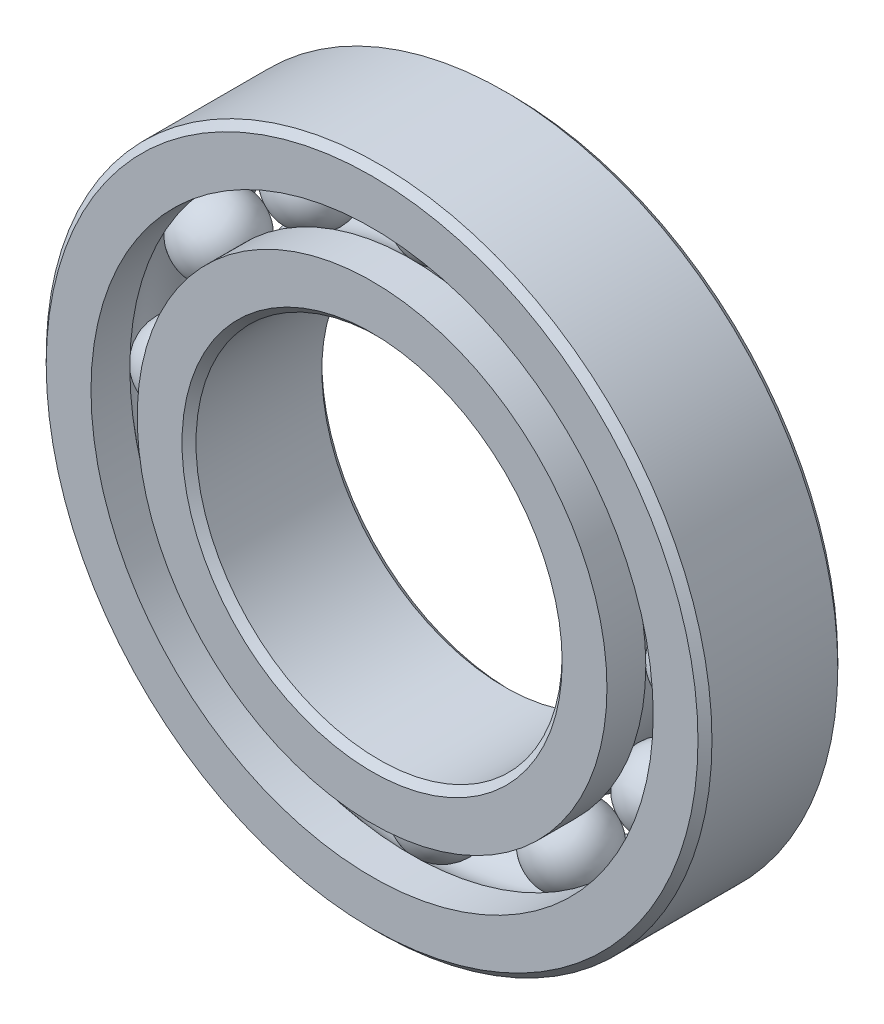
SolidWorks part; units mm, degrees
ref_plane "Front Plane" through (0, 0, 0) normal (0, 0, 1) x (1, 0, 0)
ref_plane "Top Plane" through (0, 0, 0) normal (0, 1, 0) x (1, 0, 0)
ref_plane "Right Plane" through (0, 0, 0) normal (1, 0, 0) x (0, 0, -1)
sketch "Sketch1" plane through (0, 0, 0) normal (1, 0, 0) x (0, 0, -1)
  line L0 (-10.5, 0) -> (10.5, 0) construction
  line L1 (0, 50) -> (0, -50) construction
  line L2 (9.45, 50) -> (-9.45, 50)
  line L3 (-9.45, 50) -> (-10.5, 48.95)
  line L4 (-10.5, 48.95) -> (-10.5, 42.2225)
  line L5 (-10.5, 42.2225) -> (-4.6667, 42.2225)
  line L6 (10.5, 42.2225) -> (4.6667, 42.2225)
  line L7 (10.5, 48.95) -> (10.5, 42.2225)
  line L8 (9.45, 50) -> (10.5, 48.95)
  line L9 (0, 50) -> (0, 38.75) construction
  line L10 (0, 38.75) -> (0, 27.5) construction
  arc A0 (-4.6667, 42.2225) -> (4.6667, 42.2225) centre (0, 38.75) cw
  point P14 (0, 27.5)
  dimension "D3" = 9.3333
  dimension "D1" = 45
  dimension "Width" = 21
  dimension "OD" = 100
  dimension "D2" = 1.05
  dimension "Shaft Dia" = 55
  dimension "D4" = 3.4725
revolve "Revolve1" add sketch "Sketch1" angle 360 about L0
sketch "Sketch3" plane through (0, 0, 0) normal (1, 0, 0) x (0, 0, -1)
  line L0 (-10.5, 35.2775) -> (-4.6667, 35.2775)
  line L1 (0, 50) -> (0, -50) construction
  line L2 (-10.5, 48.95) -> (-10.5, 42.2225) construction
  line L3 (-10.5, 35.2775) -> (-10.5, 28.55)
  line L4 (-9.45, 50) -> (-10.5, 48.95) construction
  line L5 (-10.5, 28.55) -> (-9.45, 27.5)
  line L6 (-9.45, 27.5) -> (9.45, 27.5)
  line L7 (9.45, 50) -> (9.45, -50) construction
  line L8 (9.45, 27.5) -> (10.5, 28.55)
  line L9 (10.5, -48.95) -> (10.5, 48.95) construction
  line L10 (10.5, 28.55) -> (10.5, 35.2775)
  line L11 (10.5, 35.2775) -> (4.6667, 35.2775)
  line L13 (9.45, 50) -> (10.5, 48.95) construction
  arc A0 (4.6667, 42.2225) -> (-4.6667, 42.2225) centre (0, 38.75) ccw construction
  arc A1 (4.6667, 35.2775) -> (-4.6667, 35.2775) centre (0, 38.75) cw
revolve "Revolve3" add sketch "Sketch3" angle 360 about L0
sketch "Sketch4" plane through (0, 0, 0) normal (1, 0, 0) x (0, 0, -1)
  line L0 (-5.8169, 38.75) -> (5.8169, 38.75)
  arc A2 (-5.8169, 38.75) -> (5.8169, 38.75) centre (0, 38.75) cw
  arc A3 (4.6667, 42.2225) -> (-4.6667, 42.2225) centre (0, 38.75) ccw construction
revolve "Revolve4" add sketch "Sketch4" angle 360 about L0
ref_axis "Axis1" through (0, 0, -10.5) along (0, 0, 1)
pattern_circular "CirPattern1" count 12 every 30 about axis through (0, 0, -10.5) along (0, 0, 1) of bodies 104
sketch "Sketch5" plane through (0, 0, 0) normal (1, 0, 0) x (0, 0, -1)
  line L0 (-10.5, 42.2225) -> (-4.6667, 42.2225) construction
  line L1 (-9.975, 42.2225) -> (-5.8169, 42.2225)
  line L2 (-9.975, 42.2225) -> (-9.975, 35.2775)
  line L3 (-9.975, 35.2775) -> (-5.8169, 35.2775)
  line L4 (-5.8169, 42.2225) -> (-5.8169, 35.2775)
  line L5 (-10.5, 35.2775) -> (-4.6667, 35.2775) construction
  line L6 (10.5, 42.2225) -> (4.6667, 42.2225) construction
  line L7 (9.975, 42.2225) -> (5.8169, 42.2225)
  line L8 (9.975, 42.2225) -> (9.975, 35.2775)
  line L9 (9.975, 35.2775) -> (5.8169, 35.2775)
  line L10 (5.8169, 42.2225) -> (5.8169, 35.2775)
  line L11 (10.5, 35.2775) -> (4.6667, 35.2775) construction
  line L12 (-9.45, 50) -> (-10.5, 48.95) construction
  point P18 (-9.975, 49.475)
equation "\"D2@Sketch1\" = \"Width@Sketch1\"*.05"
equation "\"D3@Sketch1\" = \"Width@Sketch1\"/2.25"
equation "\"D4@Sketch1\" = (((\"OD@Sketch1\"-\"Width@Sketch1\")/2)/3.25)/3.5"
equation "\"D2@CirPattern1\" = 360/\"Balls@CirPattern1\""
